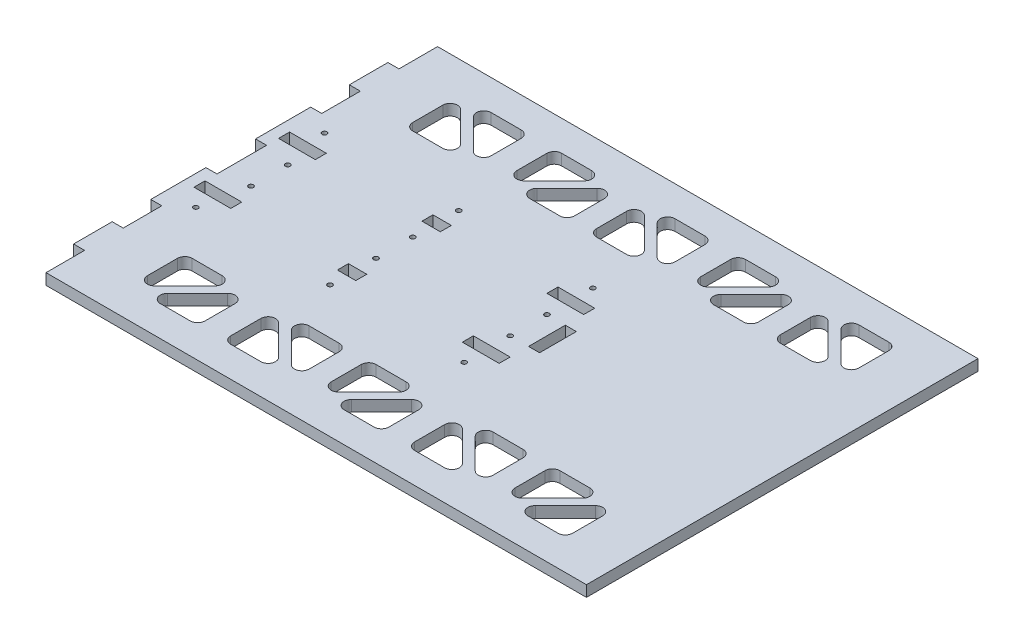
SolidWorks part; units mm, degrees
material "Balsa"
ref_plane "Front Plane" through (0, 0, 0) normal (0, 0, 1) x (1, 0, 0)
ref_plane "Top Plane" through (0, 0, 0) normal (0, 1, 0) x (1, 0, 0)
ref_plane "Right Plane" through (0, 0, 0) normal (1, 0, 0) x (0, 0, -1)
sketch "Sketch1" plane through (0, 0, 0) normal (0, 1, 0) x (1, 0, 0)
  line L0 (0, 0) -> (0, 106.5) construction
  line L1 (-150, 106.5) -> (150, 106.5)
  line L2 (-150, 106.5) -> (-150, -106.5)
  line L3 (-150, -106.5) -> (150, -106.5)
  line L4 (150, 106.5) -> (150, -106.5)
  line L5 (0, 0) -> (150, 0) construction
  dimension "D1" = 300
  dimension "D2" = 213
extrude "Boss-Extrude1" add sketch "Sketch1" along normal blind 6
sketch "Sketch2" plane through (0, 6, 0) normal (0, 1, 0) x (1, 0, 0)
  line L0 (-150, 106.5) -> (-150, -106.5) construction
  line L1 (150, 106.5) -> (-150, 106.5) construction
  line L2 (-150, 85.5) -> (-144, 85.5)
  line L3 (-150, 85.5) -> (-150, 106.5)
  line L4 (-150, 106.5) -> (-144, 106.5)
  line L6 (-144, 85.5) -> (-144, 106.5)
  line L7 (-150, -13.5) -> (-150, 0)
  line L8 (-150, 64.5) -> (-144, 64.5)
  line L9 (-150, 64.5) -> (-150, 43.5)
  line L10 (0, 0) -> (-144, 0) construction
  line L11 (-150, 43.5) -> (-144, 43.5)
  line L12 (-144, 64.5) -> (-144, 43.5)
  line L13 (-150, 13.5) -> (-144, 13.5)
  line L14 (-150, 13.5) -> (-150, 0)
  line L16 (-144, 13.5) -> (-144, -13.5)
  line L17 (-150, -13.5) -> (-144, -13.5)
  line L18 (-144, -64.5) -> (-144, -43.5)
  line L19 (-150, -43.5) -> (-144, -43.5)
  line L20 (-150, -64.5) -> (-150, -43.5)
  line L21 (-150, -64.5) -> (-144, -64.5)
  line L22 (-144, -85.5) -> (-144, -106.5)
  line L23 (-150, -106.5) -> (-144, -106.5)
  line L24 (-150, -85.5) -> (-150, -106.5)
  line L25 (-150, -85.5) -> (-144, -85.5)
  dimension "D1" = 21
  dimension "D2" = 21
  dimension "D3" = 30
  dimension "D4" = 6
  dimension "D5" = 21
extrude "Cut-Extrude1" cut sketch "Sketch2" against normal through all
sketch "Sketch3" plane through (0, 6, 0) normal (0, 1, 0) x (1, 0, 0)
  line L0 (0, 0) -> (-144, 0) construction
  line L1 (-144, 26) -> (-124, 26)
  line L2 (-144, 26) -> (-144, 20)
  line L3 (-144, 20) -> (-124, 20)
  line L4 (-124, 26) -> (-124, 20)
  line L5 (-66, 26) -> (-56, 26)
  line L6 (-66, 26) -> (-66, 20)
  line L7 (-66, 20) -> (-56, 20)
  line L8 (-56, 26) -> (-56, 20)
  line L9 (2, 26) -> (22, 26)
  line L10 (2, 26) -> (2, 20)
  line L11 (2, 20) -> (22, 20)
  line L12 (22, 26) -> (22, 20)
  line L13 (-144, -13.5) -> (-144, 13.5) construction
  line L14 (22, -26) -> (22, -20)
  line L15 (2, -20) -> (22, -20)
  line L16 (2, -26) -> (2, -20)
  line L17 (2, -26) -> (22, -26)
  line L18 (-56, -26) -> (-56, -20)
  line L19 (-66, -20) -> (-56, -20)
  line L20 (-66, -26) -> (-66, -20)
  line L21 (-66, -26) -> (-56, -26)
  line L22 (-124, -26) -> (-124, -20)
  line L23 (-144, -20) -> (-124, -20)
  line L24 (-144, -26) -> (-144, -20)
  line L25 (-144, -26) -> (-124, -26)
  dimension "D1" = 20
  dimension "D2" = 20
extrude "Cut-Extrude2" cut sketch "Sketch3" against normal through all
sketch "Sketch4" plane through (0, 6, 0) normal (0, 1, 0) x (1, 0, 0)
  line L1 (22, 10) -> (28, 10)
  line L2 (22, 10) -> (22, -10)
  line L3 (22, -10) -> (28, -10)
  line L4 (28, 10) -> (28, -10)
extrude "Cut-Extrude3" cut sketch "Sketch4" against normal through all
sketch "Sketch6" plane through (0, 6, 0) normal (0, 1, 0) x (1, 0, 0)
  circle A0 centre (-134, 35) radius 1.3
  circle A1 centre (-61, 35) radius 1.3
  circle A4 centre (12, 35) radius 1.3
  circle A6 centre (12, -35) radius 1.3
  circle A8 centre (-61, -35) radius 1.3
  circle A10 centre (-134, -35) radius 1.3
  dimension "D1" = 2.6
extrude "Cut-Extrude4" cut sketch "Sketch6" against normal through all
sketch "Sketch7" plane through (0, 6, 0) normal (0, 1, 0) x (1, 0, 0)
  line L0 (-115, 90) -> (-115, 60)
  line L1 (-115, 60) -> (-85, 60)
  line L2 (-85, 60) -> (-115, 90)
  line L3 (-108, 90) -> (-78, 60)
  line L4 (-78, 60) -> (-78, 90)
  line L5 (-78, 90) -> (-108, 90)
  line L6 (-150, 75) -> (150, 75) construction
  line L7 (-150, 85.5) -> (-150, 64.5) construction
  line L8 (150, -106.5) -> (150, 106.5) construction
  line L9 (-115, 75) -> (-78, 75) construction
  line L10 (-71, 106.5) -> (-71, -106.5) construction
  line L11 (150, 106.5) -> (-144, 106.5) construction
  line L12 (-144, -106.5) -> (150, -106.5) construction
  line L13 (-64, 90) -> (-34, 90)
  line L14 (-64, 60) -> (-64, 90)
  line L15 (-34, 90) -> (-64, 60)
  line L16 (-27, 60) -> (-57, 60)
  line L17 (-57, 60) -> (-27, 90)
  line L18 (-27, 90) -> (-27, 60)
  line L19 (-15, 90) -> (-15, 60)
  line L20 (-15, 60) -> (15, 60)
  line L21 (15, 60) -> (-15, 90)
  line L22 (-8, 90) -> (22, 60)
  line L23 (22, 60) -> (22, 90)
  line L24 (22, 90) -> (-8, 90)
  line L25 (36, 90) -> (66, 90)
  line L26 (36, 60) -> (36, 90)
  line L27 (66, 90) -> (36, 60)
  line L28 (73, 60) -> (43, 60)
  line L29 (43, 60) -> (73, 90)
  line L30 (73, 90) -> (73, 60)
  line L31 (-15, 75) -> (22, 75) construction
  line L32 (85, 90) -> (85, 60)
  line L33 (85, 60) -> (115, 60)
  line L34 (115, 60) -> (85, 90)
  line L35 (92, 90) -> (122, 60)
  line L36 (122, 60) -> (122, 90)
  line L37 (122, 90) -> (92, 90)
  line L38 (-144, 0) -> (150, 0) construction
  line L39 (-144, -13.5) -> (-144, 13.5) construction
  line L43 (-150, -75) -> (150, -75) construction
  line L44 (85, 75) -> (122, 75) construction
  line L45 (166, 90) -> (136, 60) [skipped]
  line L46 (173, 60) -> (143, 60) [skipped]
  line L47 (143, 60) -> (173, 90) [skipped]
  line L48 (173, 90) -> (173, 60) [skipped]
  line L49 (136, 90) -> (166, 90) [skipped]
  line L50 (136, 60) -> (136, 90) [skipped]
  dimension "D1" = 30
  dimension "D2" = 35
  dimension "D3" = 7
  dimension "D4" = 7
  dimension "D5" = 3
extrude "Cut-Extrude5" cut sketch "Sketch7" against normal through all
fillet "Fillet1" radius 4 30 edges at (92, 3, -90) (122, 3, -90) (122, 3, -60) (115, 3, -60) (85, 3, -90) (85, 3, -60) (73, 3, -60) (73, 3, -90) (43, 3, -60) (36, 3, -60) (66, 3, -90) (36, 3, -90) (-8, 3, -90) (22, 3, -90) (22, 3, -60) (-15, 3, -60) (15, 3, -60) (-15, 3, -90) (-57, 3, -60) (-27, 3, -60) (-27, 3, -90) (-34, 3, -90) (-64, 3, -90) (-64, 3, -60) (-78, 3, -60) (-78, 3, -90) (-108, 3, -90) (-115, 3, -60) (-85, 3, -60) (-115, 3, -90)
mirror "Mirror1" about plane through (0, 0, 0) normal (0, 0, 1) of "Fillet1", "Cut-Extrude5"
sketch "Sketch8" plane through (0, 6, 0) normal (0, 1, 0) x (1, 0, 0)
  line L0 (-144, 0) -> (150, 0) construction
  line L1 (-144, -13.5) -> (-144, 13.5) construction
  line L2 (150, -106.5) -> (150, 106.5) construction
  circle A0 centre (-129, -10) radius 1.3
  circle A2 centre (-61, -10) radius 1.3
  circle A4 centre (12, -10) radius 1.3
  circle A6 centre (-129, 10) radius 1.3
  circle A7 centre (-61, 10) radius 1.3
  circle A8 centre (12, 10) radius 1.3
  dimension "D1" = 2.6
extrude "Cut-Extrude6" cut sketch "Sketch8" against normal through all
